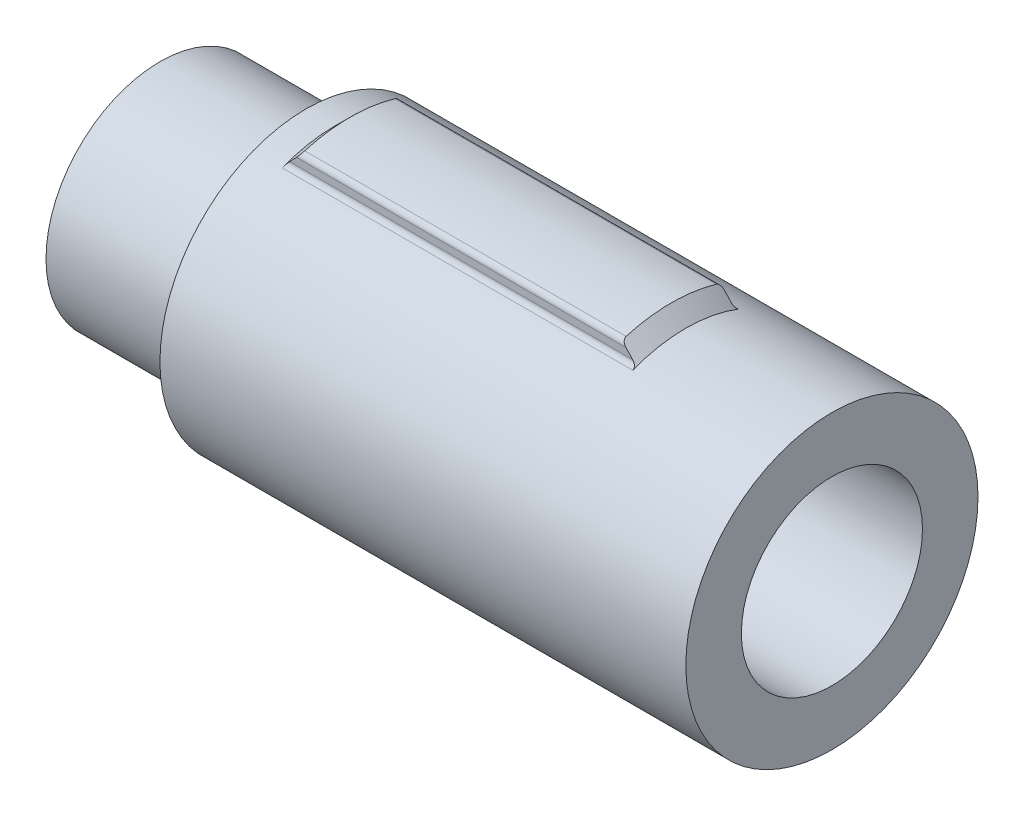
SolidWorks part; units mm, degrees
ref_plane "前视基准面" through (0, 0, 0) normal (0, 0, 1) x (1, 0, 0)
ref_plane "上视基准面" through (0, 0, 0) normal (0, 1, 0) x (1, 0, 0)
ref_plane "右视基准面" through (0, 0, 0) normal (1, 0, 0) x (0, 0, -1)
other "Configuration Table"
sketch "草图1" plane through (0, 0, 0) normal (1, 0, 0) x (0, 0, -1)
  circle A0 centre (0, 0) radius 5
  dimension "D1" = 10
extrude "凸台-拉伸1" add sketch "草图1" along normal blind 18
sketch "草图3" plane through (18, 0, 0) normal (1, 0, 0) x (0, 0, -1)
  circle A0 centre (0, 0) radius 3.1
  dimension "D1" = 6.2
extrude "切除-拉伸1" cut sketch "草图3" against normal blind 17
sketch "草图5" plane through (1, 0, 0) normal (1, 0, 0) x (0, 0, -1)
  line L1 (-1.6882, 2.6) -> (1.6882, 2.6)
  line L2 (-1.6882, 2.6) -> (-1.6882, 5.2345)
  line L3 (1.6882, 2.6) -> (1.6882, 5.2345)
  line L4 (0, 5.5) -> (1.6882, 5.5) construction
  line L5 (-1.6882, 5.5) -> (0, 5.5) construction
  line L6 (-1.6882, 5.2345) -> (-1.6882, 5.5) construction
  line L7 (1.6882, 5.2345) -> (1.6882, 5.5) construction
  circle A0 centre (0, 0) radius 3.1 construction
  arc A1 (1.6882, 2.6) -> (-1.6882, 2.6) centre (0, 0) ccw construction
  arc A2 (-1.6882, 2.6) -> (1.6882, 2.6) centre (0, 0) ccw construction
  arc A5 (-1.6882, 5.2345) -> (1.6882, 5.2345) centre (0, 0) ccw construction
  circle A6 centre (0, 0) radius 5.5
  arc A7 (1.6882, 5.2345) -> (-1.6882, 5.2345) centre (0, 0) ccw
  dimension "D1" = 2.6
  dimension "D2" = 0.5
extrude "凸台-拉伸2" add sketch "草图5" along normal blind 12
sketch "草图8" plane through (0, 0, 0) normal (-1, 0, 0) x (0, 0, 1)
  circle A0 centre (0, 0) radius 3.9
  dimension "D1" = 7.8
extrude "凸台-拉伸4" add sketch "草图8" along normal blind 5
sketch "草图9" plane through (-5, 0, 0) normal (-1, 0, 0) x (0, 0, 1)
  circle A0 centre (0, 0) radius 2.6
  dimension "D1" = 5.2
extrude "切除-拉伸2" cut sketch "草图9" against normal blind 5
sketch "草图10" plane through (0, 0, 0) normal (-1, 0, 0) x (0, 0, 1)
  line L1 (0.664, 1.15) -> (-0.664, 1.15)
  line L2 (-0.664, 1.15) -> (-1.3279, 0)
  line L3 (-1.3279, 0) -> (-0.664, -1.15)
  line L4 (-0.664, -1.15) -> (0.664, -1.15)
  line L5 (0.664, -1.15) -> (1.3279, 0)
  line L6 (1.3279, 0) -> (0.664, 1.15)
  circle A0 centre (0, 0) radius 1.15 construction
  dimension "D1" = 2.3
extrude "凸台-拉伸5" add sketch "草图10" along normal blind 3
fillet "圆角1" radius 0.2 4 edges at (7, 4.7064, -1.6882) (7, 5.2345, -1.6882) (7, 4.7064, 1.6882) (7, 5.2345, 1.6882)
chamfer "倒角1" distance 0.5 angle 45 3 edges at (13, 5.5, 0) (1, 5.5, 0) (13, 2.6, 0)
